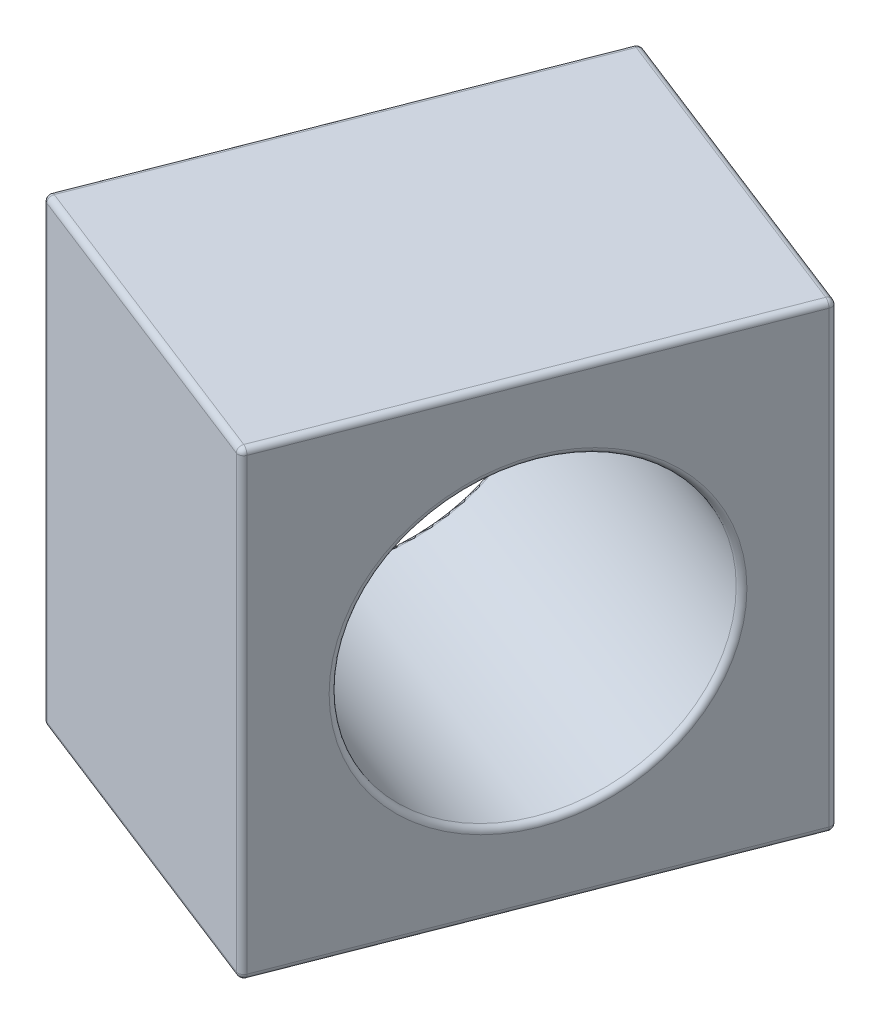
SolidWorks part; units mm, degrees
ref_plane "Front Plane" through (0, 0, 0) normal (0, 0, 1) x (1, 0, 0)
ref_plane "Top Plane" through (0, 0, 0) normal (0, 1, 0) x (1, 0, 0)
ref_plane "Right Plane" through (0, 0, 0) normal (1, 0, 0) x (0, 0, -1)
sketch "Sketch1" plane through (0, 0, 0) normal (0, 1, 0) x (1, 0, 0)
  line L0 (0, 0) -> (640, 0) construction
  line L1 (0, 0) -> (591.2829, 244.9174)
  line L2 (0, 0) -> (591.2829, -244.9174)
  line L3 (0, 0) -> (244.9174, -591.2829)
  line L4 (0, 0) -> (-244.9174, -591.2829)
  line L5 (0, 0) -> (-591.2829, -244.9174)
  line L6 (0, 0) -> (-591.2829, 244.9174)
  line L7 (0, 0) -> (-244.9174, 591.2829)
  line L8 (0, 0) -> (244.9174, 591.2829)
  line L9 (0, 145) -> (55, 145) construction
  line L10 (0, 0) -> (100, 0) construction
  line L11 (0, 0) -> (0, 145) construction
  line L14 (100, 0) -> (100, 145) construction
  circle A0 centre (0, 0) radius 640 construction
  point P15 (0, 0)
  dimension "D1" = 1280
  dimension "D2" = 22.5
  dimension "D4" = 145
  dimension "D5" = 100
  dimension "D6" = 55
  dimension "D3" = 8
sketch "Sketch2" plane through (0, 0, 0) normal (0, 1, 0) x (1, 0, 0)
  line L0 (-486.9956, 169.5033) -> (-66.9956, 169.5033) construction
  line L1 (-188.7141, -86.1278) -> (-188.7141, 241.8722) construction
  line L2 (525.6625, -1048.8053) -> (466.9027, -726.1115) construction
sketch "Sketch3" plane through (0, 0, 0) normal (0, 1, 0) x (1, 0, 0)
  line L0 (0, 0) -> (381.2468, 0) construction
  line L5 (0, 0) -> (0, 199.4415) construction
  line L6 (-10.2736, 158.9263) -> (10.2736, 158.9263)
  line L7 (10.2736, 158.9263) -> (13.1995, 163.9003)
  line L8 (13.1995, 163.9003) -> (45.5131, 148.2994)
  line L9 (45.5131, 148.2994) -> (66.2904, 80.9335)
  line L10 (66.2904, 80.9335) -> (73.8622, 80.9335)
  line L11 (73.8622, 80.9335) -> (86.8684, 42.4396)
  line L12 (86.8684, 42.4396) -> (86.8684, 30.0712)
  line L13 (86.8684, 30.0712) -> (81.3965, 24.5993)
  line L14 (81.3965, 24.5993) -> (81.3965, -24.5993)
  line L15 (-5.8349, 67.4929) -> (5.8349, 67.4929) construction
  line L16 (16.6008, 64.1674) -> (16.6008, 27.6557) construction
  line L17 (16.6008, 27.6557) -> (13.2646, 22.809) construction
  line L18 (13.2646, 22.809) -> (13.2646, -22.809) construction
  line L19 (5.8349, 128.0146) -> (5.8349, 107.4452)
  line L22 (5.8349, 107.4452) -> (9.2702, 107.4452)
  line L25 (9.2702, 107.4452) -> (10.663, 103.7163)
  line L26 (10.663, 103.7163) -> (20.7578, 101.0699)
  line L27 (20.7578, 101.0699) -> (32.199, 111.7601)
  line L28 (32.199, 111.7601) -> (32.199, 123.5038)
  line L29 (32.199, 123.5038) -> (24.9078, 123.5038)
  line L30 (24.9078, 123.5038) -> (13.8412, 132.5856)
  line L31 (13.8412, 132.5856) -> (9.2702, 132.5856)
  line L32 (9.2702, 132.5856) -> (5.8349, 128.0146)
  line L33 (41.9414, 39.7891) -> (51.4866, 54.1602)
  line L34 (51.4866, 54.1602) -> (55.4027, 54.1602)
  line L35 (55.4027, 54.1602) -> (58.1637, 51.3993)
  line L36 (58.1637, 51.3993) -> (58.1637, 43.1872)
  line L37 (58.1637, 43.1872) -> (66.3555, 28.462)
  line L38 (66.3555, 28.462) -> (66.3555, 24.0728)
  line L39 (66.3555, 24.0728) -> (62.2596, 17.9061)
  line L40 (62.2596, 17.9061) -> (47.8497, 18.1669)
  line L41 (47.8497, 18.1669) -> (41.9414, 27.1878)
  line L42 (41.9414, 27.1878) -> (41.9414, 39.7891)
  line L43 (-41.9414, 27.1878) -> (-41.9414, 39.7891)
  line L44 (-47.8497, 18.1669) -> (-41.9414, 27.1878)
  line L45 (-62.2596, 17.9061) -> (-47.8497, 18.1669)
  line L46 (-66.3555, 24.0728) -> (-62.2596, 17.9061)
  line L47 (-66.3555, 28.462) -> (-66.3555, 24.0728)
  line L48 (-58.1637, 43.1872) -> (-66.3555, 28.462)
  line L49 (-58.1637, 51.3993) -> (-58.1637, 43.1872)
  line L50 (-55.4027, 54.1602) -> (-58.1637, 51.3993)
  line L51 (-51.4866, 54.1602) -> (-55.4027, 54.1602)
  line L52 (-41.9414, 39.7891) -> (-51.4866, 54.1602)
  line L53 (-9.2702, 132.5856) -> (-5.8349, 128.0146)
  line L54 (-13.8412, 132.5856) -> (-9.2702, 132.5856)
  line L55 (-24.9078, 123.5038) -> (-13.8412, 132.5856)
  line L56 (-32.199, 123.5038) -> (-24.9078, 123.5038)
  line L57 (-32.199, 111.7601) -> (-32.199, 123.5038)
  line L58 (-20.7578, 101.0699) -> (-32.199, 111.7601)
  line L59 (-10.663, 103.7163) -> (-20.7578, 101.0699)
  line L60 (-9.2702, 107.4452) -> (-10.663, 103.7163)
  line L61 (-5.8349, 107.4452) -> (-9.2702, 107.4452)
  line L62 (-5.8349, 128.0146) -> (-5.8349, 107.4452)
  line L63 (-13.2646, 22.809) -> (-13.2646, -22.809) construction
  line L64 (-16.6008, 27.6557) -> (-13.2646, 22.809) construction
  line L65 (-16.6008, 64.1674) -> (-16.6008, 27.6557) construction
  line L66 (-81.3965, 24.5993) -> (-81.3965, -24.5993)
  line L67 (-86.8684, 30.0712) -> (-81.3965, 24.5993)
  line L68 (-86.8684, 42.4396) -> (-86.8684, 30.0712)
  line L69 (-73.8622, 80.9335) -> (-86.8684, 42.4396)
  line L70 (-66.2904, 80.9335) -> (-73.8622, 80.9335)
  line L71 (-45.5131, 148.2994) -> (-66.2904, 80.9335)
  line L72 (-13.1995, 163.9003) -> (-45.5131, 148.2994)
  line L73 (-10.2736, 158.9263) -> (-13.1995, 163.9003)
  line L74 (-10.2736, -158.9263) -> (-13.1995, -163.9003)
  line L75 (-13.1995, -163.9003) -> (-45.5131, -148.2994)
  line L76 (-45.5131, -148.2994) -> (-66.2904, -80.9335)
  line L77 (-66.2904, -80.9335) -> (-73.8622, -80.9335)
  line L78 (-73.8622, -80.9335) -> (-86.8684, -42.4396)
  line L79 (-86.8684, -42.4396) -> (-86.8684, -30.0712)
  line L80 (-86.8684, -30.0712) -> (-81.3965, -24.5993)
  line L81 (-16.6008, -64.1674) -> (-16.6008, -27.6557) construction
  line L82 (-16.6008, -27.6557) -> (-13.2646, -22.809) construction
  line L83 (-5.8349, -128.0146) -> (-5.8349, -107.4452)
  line L84 (-5.8349, -107.4452) -> (-9.2702, -107.4452)
  line L85 (-9.2702, -107.4452) -> (-10.663, -103.7163)
  line L86 (-10.663, -103.7163) -> (-20.7578, -101.0699)
  line L87 (-20.7578, -101.0699) -> (-32.199, -111.7601)
  line L88 (-32.199, -111.7601) -> (-32.199, -123.5038)
  line L89 (-32.199, -123.5038) -> (-24.9078, -123.5038)
  line L90 (-24.9078, -123.5038) -> (-13.8412, -132.5856)
  line L91 (-13.8412, -132.5856) -> (-9.2702, -132.5856)
  line L92 (-9.2702, -132.5856) -> (-5.8349, -128.0146)
  line L93 (-41.9414, -39.7891) -> (-51.4866, -54.1602)
  line L94 (-51.4866, -54.1602) -> (-55.4027, -54.1602)
  line L95 (-55.4027, -54.1602) -> (-58.1637, -51.3993)
  line L96 (-58.1637, -51.3993) -> (-58.1637, -43.1872)
  line L97 (-58.1637, -43.1872) -> (-66.3555, -28.462)
  line L98 (-66.3555, -28.462) -> (-66.3555, -24.0728)
  line L99 (-66.3555, -24.0728) -> (-62.2596, -17.9061)
  line L100 (-62.2596, -17.9061) -> (-47.8497, -18.1669)
  line L101 (-47.8497, -18.1669) -> (-41.9414, -27.1878)
  line L102 (-41.9414, -27.1878) -> (-41.9414, -39.7891)
  line L103 (41.9414, -27.1878) -> (41.9414, -39.7891)
  line L104 (47.8497, -18.1669) -> (41.9414, -27.1878)
  line L105 (62.2596, -17.9061) -> (47.8497, -18.1669)
  line L106 (66.3555, -24.0728) -> (62.2596, -17.9061)
  line L107 (66.3555, -28.462) -> (66.3555, -24.0728)
  line L108 (58.1637, -43.1872) -> (66.3555, -28.462)
  line L109 (58.1637, -51.3993) -> (58.1637, -43.1872)
  line L110 (55.4027, -54.1602) -> (58.1637, -51.3993)
  line L111 (51.4866, -54.1602) -> (55.4027, -54.1602)
  line L112 (41.9414, -39.7891) -> (51.4866, -54.1602)
  line L113 (9.2702, -132.5856) -> (5.8349, -128.0146)
  line L114 (13.8412, -132.5856) -> (9.2702, -132.5856)
  line L115 (24.9078, -123.5038) -> (13.8412, -132.5856)
  line L116 (32.199, -123.5038) -> (24.9078, -123.5038)
  line L117 (32.199, -111.7601) -> (32.199, -123.5038)
  line L118 (20.7578, -101.0699) -> (32.199, -111.7601)
  line L119 (10.663, -103.7163) -> (20.7578, -101.0699)
  line L120 (9.2702, -107.4452) -> (10.663, -103.7163)
  line L121 (5.8349, -107.4452) -> (9.2702, -107.4452)
  line L122 (5.8349, -128.0146) -> (5.8349, -107.4452)
  line L123 (16.6008, -27.6557) -> (13.2646, -22.809) construction
  line L124 (16.6008, -64.1674) -> (16.6008, -27.6557) construction
  line L125 (-5.8349, -67.4929) -> (5.8349, -67.4929) construction
  line L126 (86.8684, -30.0712) -> (81.3965, -24.5993)
  line L127 (86.8684, -42.4396) -> (86.8684, -30.0712)
  line L128 (73.8622, -80.9335) -> (86.8684, -42.4396)
  line L129 (66.2904, -80.9335) -> (73.8622, -80.9335)
  line L130 (45.5131, -148.2994) -> (66.2904, -80.9335)
  line L131 (13.1995, -163.9003) -> (45.5131, -148.2994)
  line L132 (10.2736, -158.9263) -> (13.1995, -163.9003)
  line L133 (-10.2736, -158.9263) -> (10.2736, -158.9263)
  line L134 (-5.3457, 68.4929) -> (5.3457, 68.4929)
  line L135 (17.6008, 64.1674) -> (17.6008, 27.3448)
  line L136 (17.6008, 27.3448) -> (14.2646, 22.498)
  line L137 (14.2646, 22.498) -> (14.2646, -22.498)
  line L138 (-17.6008, 64.1674) -> (-17.6008, 27.3448)
  line L139 (-17.6008, 27.3448) -> (-14.2646, 22.498)
  line L140 (-5.3457, 68.4929) -> (5.3457, 68.4929) construction
  line L141 (14.2646, 22.498) -> (14.2646, -22.498) construction
  line L142 (17.6008, -27.3448) -> (14.2646, -22.498) construction
  line L143 (17.6008, -64.1674) -> (17.6008, -27.3448) construction
  line L144 (-14.2646, 22.498) -> (-14.2646, -22.498)
  line L145 (17.6008, -64.1674) -> (17.6008, -27.3448)
  line L146 (17.6008, -27.3448) -> (14.2646, -22.498)
  line L147 (-17.6008, -27.3448) -> (-14.2646, -22.498)
  line L148 (-17.6008, -64.1674) -> (-17.6008, -27.3448)
  line L149 (-5.3457, -68.4929) -> (5.3457, -68.4929)
  arc A0 (5.8349, 67.4929) -> (16.6008, 64.0252) centre (10.663, 64.0364) cw construction
  arc A5 (-5.8349, 67.4929) -> (-16.6008, 64.0252) centre (-10.663, 64.0364) ccw construction
  arc A6 (-5.8349, -67.4929) -> (-16.6008, -64.0252) centre (-10.663, -64.0364) cw construction
  arc A7 (5.8349, -67.4929) -> (16.6008, -64.0252) centre (10.663, -64.0364) ccw construction
  arc A8 (-5.3457, 68.4929) -> (-17.6008, 64.0234) centre (-10.663, 64.0364) ccw
  arc A9 (5.3457, 68.4929) -> (17.6008, 64.0234) centre (10.663, 64.0364) cw
  arc A10 (-5.3457, 68.4929) -> (-17.6008, 64.0234) centre (-10.663, 64.0364) ccw construction
  arc A11 (5.3457, -68.4929) -> (17.6008, -64.0234) centre (10.663, -64.0364) ccw
  arc A12 (-5.3457, -68.4929) -> (-17.6008, -64.0234) centre (-10.663, -64.0364) cw
  ellipse E0 centre (11.3851, 149.6854) end of major axis (12.0553, 155.2702) minor radius 3.0047
  ellipse E1 centre (33.6925, 82.363) end of major axis (41.1096, 88.3895) minor radius 4.3287
  ellipse E2 centre (44.8955, 74.0187) end of major axis (51.4866, 79.374) minor radius 4.6847
  ellipse E3 centre (66.3555, 66.447) end of major axis (67.1471, 72.2416) minor radius 3.5711
  ellipse E4 centre (-66.3555, 66.447) end of major axis (-67.1471, 72.2416) minor radius 3.5711
  ellipse E5 centre (-44.8955, 74.0187) end of major axis (-51.4866, 79.374) minor radius 4.6847
  ellipse E6 centre (-33.6925, 82.363) end of major axis (-41.1096, 88.3895) minor radius 4.3287
  ellipse E7 centre (-11.3851, 149.6854) end of major axis (-12.0553, 155.2702) minor radius 3.0047
  ellipse E8 centre (-11.3851, -149.6854) end of major axis (-12.0553, -155.2702) minor radius 3.0047
  ellipse E9 centre (-33.6925, -82.363) end of major axis (-41.1096, -88.3895) minor radius 4.3287
  ellipse E10 centre (-44.8955, -74.0187) end of major axis (-51.4866, -79.374) minor radius 4.6847
  ellipse E11 centre (-66.3555, -66.447) end of major axis (-67.1471, -72.2416) minor radius 3.5711
  ellipse E12 centre (66.3555, -66.447) end of major axis (67.1471, -72.2416) minor radius 3.5711
  ellipse E13 centre (44.8955, -74.0187) end of major axis (51.4866, -79.374) minor radius 4.6847
  ellipse E14 centre (33.6925, -82.363) end of major axis (41.1096, -88.3895) minor radius 4.3287
  ellipse E15 centre (11.3851, -149.6854) end of major axis (12.0553, -155.2702) minor radius 3.0047
  point P117 (0, 67.4929)
  point P126 (0, 158.9263)
  point P180 (0, -158.9263)
  point P181 (0, -67.4929)
  point P190 (-81.3965, 0)
  point P193 (-13.2646, 0)
  point P234 (13.2646, 0)
  point P237 (81.3965, 0)
  point P261 (0, 68.4929)
  point P271 (14.2646, 0)
  point P274 (-14.2646, 0)
  dimension "D1" = 1
sketch "Sketch4" plane through (0, 0, 0) normal (0, 1, 0) x (1, 0, 0)
  line L0 (0, 0) -> (81.2255, 0) construction
  line L1 (0, 0) -> (0, 97.3086) construction
  line L2 (0, 0) -> (0, 199.4415) construction
  line L3 (-10.1399, 86.6928) -> (10.1399, 86.6928)
  line L4 (10.1399, 86.6928) -> (16.0235, 80.8091)
  line L5 (16.0235, 80.8091) -> (23.9736, 57.3032)
  line L6 (23.9736, 57.3032) -> (23.9736, 47.8894)
  line L7 (23.9736, 47.8894) -> (21.6776, 47.8894)
  line L8 (21.6776, 47.8894) -> (21.6776, 27.2256)
  line L9 (21.6776, 27.2256) -> (27.5382, 22.1416)
  line L10 (27.5382, 22.1416) -> (27.5382, 14.9676)
  line L11 (27.5382, 14.9676) -> (23.9736, 10.8585)
  line L12 (23.9736, 10.8585) -> (23.9736, -10.8585)
  line L13 (-23.9736, 10.8585) -> (-23.9736, -10.8585)
  line L14 (-27.5382, 14.9676) -> (-23.9736, 10.8585)
  line L15 (-27.5382, 22.1416) -> (-27.5382, 14.9676)
  line L16 (-21.6776, 27.2256) -> (-27.5382, 22.1416)
  line L17 (-21.6776, 47.8894) -> (-21.6776, 27.2256)
  line L18 (-23.9736, 47.8894) -> (-21.6776, 47.8894)
  line L19 (-23.9736, 57.3032) -> (-23.9736, 47.8894)
  line L20 (-16.0235, 80.8091) -> (-23.9736, 57.3032)
  line L21 (-10.1399, 86.6928) -> (-16.0235, 80.8091)
  line L22 (-10.1399, -86.6928) -> (-16.0235, -80.8091)
  line L23 (-16.0235, -80.8091) -> (-23.9736, -57.3032)
  line L24 (-23.9736, -57.3032) -> (-23.9736, -47.8894)
  line L25 (-23.9736, -47.8894) -> (-21.6776, -47.8894)
  line L26 (-21.6776, -47.8894) -> (-21.6776, -27.2256)
  line L27 (-21.6776, -27.2256) -> (-27.5382, -22.1416)
  line L28 (-27.5382, -22.1416) -> (-27.5382, -14.9676)
  line L29 (-27.5382, -14.9676) -> (-23.9736, -10.8585)
  line L30 (27.5382, -14.9676) -> (23.9736, -10.8585)
  line L31 (27.5382, -22.1416) -> (27.5382, -14.9676)
  line L32 (21.6776, -27.2256) -> (27.5382, -22.1416)
  line L33 (21.6776, -47.8894) -> (21.6776, -27.2256)
  line L34 (23.9736, -47.8894) -> (21.6776, -47.8894)
  line L35 (23.9736, -57.3032) -> (23.9736, -47.8894)
  line L36 (16.0235, -80.8091) -> (23.9736, -57.3032)
  line L37 (10.1399, -86.6928) -> (16.0235, -80.8091)
  line L38 (-10.1399, -86.6928) -> (10.1399, -86.6928)
  point P3 (0, -86.6928)
  point P27 (0, 86.6928)
  point P37 (-23.9736, 0)
  point P38 (23.9736, 0)
sketch "Sketch5" plane through (0, 0, 0) normal (0, 1, 0) x (1, 0, 0)
  line L0 (0, 68.4929) -> (0, 86.6928) construction
  line L1 (15.4511, 110) -> (223.3697, 546.0887)
  line L2 (0, 0) -> (0, 251.8084) construction
  line L3 (0, 110) -> (47.9221, 110) construction
  line L5 (244.9174, 616.9519) -> (262.4572, 609.0616) construction
  line L6 (262.4572, 609.0616) -> (269.1565, 599.6825) construction
  line L7 (269.1565, 599.6825) -> (256.4381, 571.4103) construction
  line L8 (256.4381, 571.4103) -> (244.9174, 563.1812) construction
  line L9 (244.9174, 563.1812) -> (221.08, 517.0826) construction
  line L10 (221.08, 517.0826) -> (201.6817, 527.1134) construction
  line L11 (201.6817, 527.1134) -> (221.6088, 571.4103) construction
  line L12 (221.6088, 571.4103) -> (218.2415, 584.6462) construction
  line L13 (218.2415, 584.6462) -> (232.4366, 616.2011) construction
  line L14 (232.4366, 616.2011) -> (244.9174, 616.9519) construction
  line L15 (244.9174, 591.2829) -> (309.3694, 564.586) construction
  line L16 (269.6266, 526.9284) -> (173.6132, 566.6985) construction
  line L18 (0, 0) -> (107.3069, 0) construction
  dimension "D1" = 110
  dimension "D2" = 50
sketch "Sketch6" plane through (0, 0, 0) normal (0, 1, 0) x (1, 0, 0)
  line L1 (27.9119, 24.7148) -> (544.6401, 226.6863)
  circle A0 centre (0, 0) radius 640 construction
  circle A1 centre (0, 0) radius 640 construction
  circle A3 centre (0, 0) radius 589.9318 construction
  dimension "D1" = 50.0682
sketch "Sketch19" plane through (0, 0, 0) normal (0, 1, 0) x (1, 0, 0)
  line L0 (128.4599, 309.2664) -> (271.805, 137.4916)
  line L5 (26.7343, 104.6204) -> (234.6528, 540.7091)
  line L6 (26.7343, 104.6204) -> (234.6528, 540.7091) construction
  line L7 (4.1679, 115.3796) -> (212.0865, 551.4683)
  line L8 (4.1679, 115.3796) -> (212.0865, 551.4683) construction
  line L9 (20.631, 43.3425) -> (537.3592, 245.3139)
  line L10 (32.4624, 13.0726) -> (549.1907, 215.044)
  line L11 (32.4624, 13.0726) -> (549.1907, 215.044) construction
  line L12 (23.3613, 36.3571) -> (540.0895, 238.3286)
  line L13 (23.3613, 36.3571) -> (540.0895, 238.3286) construction
  line L14 (20.631, 43.3425) -> (537.3592, 245.3139) construction
  line L15 (30.1192, 103.0065) -> (238.0378, 539.0952)
  line L16 (30.1192, 103.0065) -> (238.0378, 539.0952) construction
  line L22 (21.9961, 39.8498) -> (538.7244, 241.8213)
  line L23 (21.9961, 39.8498) -> (538.7244, 241.8213) construction
  line L24 (33.5042, 101.3926) -> (241.4227, 537.4813)
  line L25 (33.5042, 101.3926) -> (241.4227, 537.4813) construction
  dimension "D1" = 12.5
  dimension "D2" = 12.5
  dimension "D3" = 12.5
  dimension "D4" = 12.5
  dimension "D5" = 16.25
  dimension "D8" = 16.25
  dimension "D10" = 20
  dimension "D11" = 20
sketch "Sketch20" plane through (0, 0, 0) normal (0, 1, 0) x (1, 0, 0)
  line L0 (27.9119, 24.7148) -> (544.6401, 226.6863) construction
  line L1 (27.9119, 24.7148) -> (544.6401, 226.6863) construction
  line L2 (271.0309, 98.2683) -> (298.9724, 109.1897)
  line L3 (256.4691, 135.5236) -> (284.4106, 146.4449)
  line L4 (298.9724, 109.1897) -> (284.4106, 146.4449)
  line L5 (285.0016, 103.729) -> (270.4398, 140.9843) construction
  line L6 (271.0309, 98.2683) -> (256.4691, 135.5236)
  line L7 (20.631, 43.3425) -> (537.3592, 245.3139) construction
  line L8 (35.1928, 6.0872) -> (551.921, 208.0587) construction
  dimension "D1" = 20
  dimension "D2" = 20
  dimension "D3" = 15
  dimension "D4" = 15
extrude "Boss-Extrude1" add sketch "Sketch20" along normal blind 20 and the other way blind 20
sweep "Cut-Sweep1" cut path "Sketch6" circular profile diameter 27 parameters "D3"=27
sweep "Cut-Sweep2" cut path "Sketch19" circular profile diameter 12 parameters "D3"=12
fillet "Fillet1" radius 0.5 15 edges at (291.6915, -20, -127.8173) (291.6915, 20, -127.8173) (285.0016, -20, -103.729) (285.0016, 20, -103.729) (298.9724, 0, -109.1897) (263.75, -20, -116.896) (263.75, 20, -116.896) (271.0309, 0, -98.2683) (268.6646, 0, -104.3223) (270.4398, -20, -140.9843) (284.4106, 0, -146.4449) (270.4398, 20, -140.9843) (256.4691, 0, -135.5236) (275.1641, 0, -142.8308) (286.7768, 0, -140.391)
mirror "Mirror1" about plane through (0, 0, 0) normal (1, 0, 0) of bodies 111 112
delete or keep bodies "Body-Delete/Keep 1" type delete bodies bodies 111
